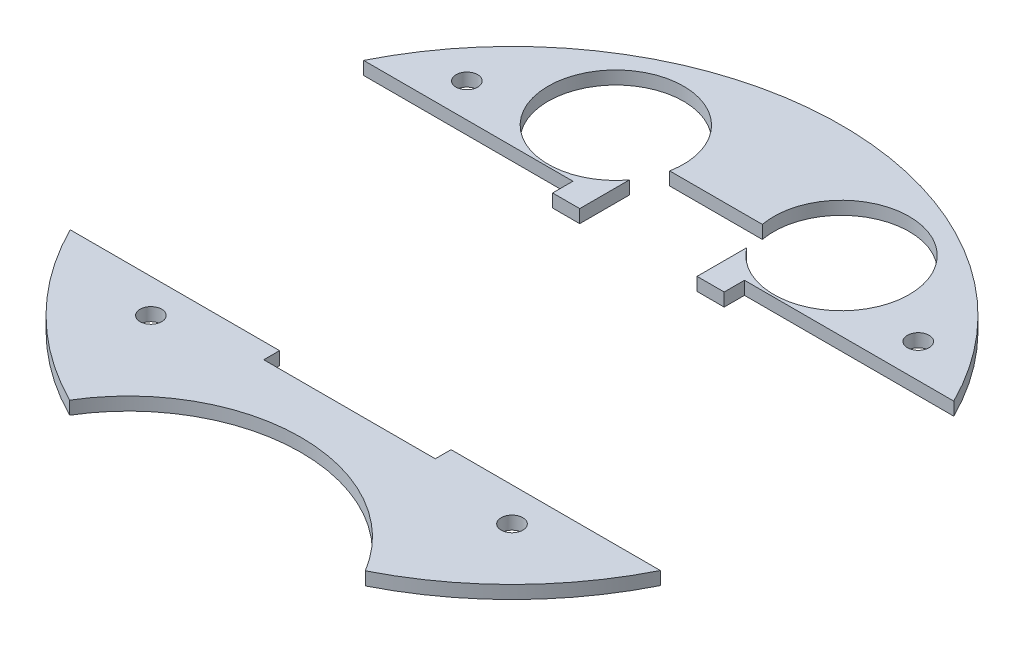
SolidWorks part; units mm, degrees
material "Acrylic (Medium-high impact)"
ref_plane "Front Plane" through (0, 0, 0) normal (0, 0, 1) x (1, 0, 0)
ref_plane "Top Plane" through (0, 0, 0) normal (0, 1, 0) x (1, 0, 0)
ref_plane "Right Plane" through (0, 0, 0) normal (1, 0, 0) x (0, 0, -1)
sketch "Sketch1" plane through (0, 0, 0) normal (0, 1, 0) x (1, 0, 0)
  line L0 (0, -85) -> (-32.7511, -65.2408) construction
  line L1 (0, -85) -> (0, 0) construction
  arc A0 (32.7511, -65.2408) -> (-32.7511, -65.2408) centre (0, 0) ccw
  arc A1 (32.7511, -65.2408) -> (-32.7511, -65.2408) centre (0, -85) ccw
  dimension "D1" = 146
  dimension "D2" = 76.5
  dimension "D3" = 85
extrude "Boss-Extrude1" add sketch "Sketch1" along normal blind 2.9
sketch "solenoid placement" plane through (0, 2.9, 0) normal (0, 1, 0) x (1, 0, 0)
  line L4 (-19, -36) -> (19, -36)
  line L5 (-19, -36) -> (19, -36)
  line L6 (19, -36) -> (19, 28)
  line L7 (19, -36) -> (19, 28)
  line L8 (19, 28) -> (-19, 28)
  line L9 (19, 28) -> (-19, 28)
  line L10 (-19, 28) -> (-19, -36)
  line L11 (-19, 28) -> (-19, -36)
  circle A1 centre (0, 0) radius 73 construction
  arc A2 (32.7511, -65.2408) -> (-32.7511, -65.2408) centre (0, 0) ccw construction
  dimension "D1" = 0
extrude "Cut-Extrude1" cut sketch "solenoid placement" against normal through all
sketch "Sketch3" plane through (0, 2.9, 0) normal (0, 1, 0) x (1, 0, 0)
  circle A1 centre (25, 48) radius 12
  circle A2 centre (-25, 48) radius 12
  dimension "D1" = 24
extrude "Cut-Extrude3" cut sketch "Sketch3" against normal through all
sketch "Sketch4" plane through (0, 5.8, 0) normal (0, 1, 0) x (1, 0, 0)
  circle A1 centre (40, -40) radius 2.4
  circle A2 centre (40, -40) radius 2.4
  circle A3 centre (-40, -40) radius 2.4
  circle A4 centre (-40, -40) radius 2.4
  circle A5 centre (-50, 40) radius 2.4
  circle A6 centre (-50, 40) radius 2.4
  circle A7 centre (50, 40) radius 2.4
  circle A8 centre (50, 40) radius 2.4
  dimension "D1" = 0
  dimension "D2" = 0
  dimension "D3" = 0
  dimension "D4" = 0
extrude "Cut-Extrude4" cut sketch "Sketch4" against normal through all
sketch "Sketch2" plane through (0, 2.9, 0) normal (0, 1, 0) x (1, 0, 0)
  line L0 (-19, 28) -> (-19, 32.5)
  line L1 (-73, -32.5) -> (73, -32.5)
  line L2 (-73, -32.5) -> (-73, 32.5)
  line L3 (-73, 32.5) -> (-19, 32.5)
  line L4 (73, -32.5) -> (73, 32.5)
  line L5 (-73, -32.5) -> (73, 32.5) construction
  line L6 (-73, 32.5) -> (73, -32.5) construction
  line L7 (19, 28) -> (19, 32.5)
  line L8 (19, 28) -> (-19, 28)
  line L9 (19, 32.5) -> (73, 32.5)
  arc A0 (32.7511, -65.2408) -> (-32.7511, -65.2408) centre (0, 0) ccw construction
  point P0 (0, 0)
  dimension "D1" = 65
extrude "Cut-Extrude2" cut sketch "Sketch2" against normal through all
sketch "Sketch5" plane through (0, 2.9, 0) normal (0, 1, 0) x (1, 0, 0)
  line L4 (-13, 28) -> (13, 28)
  line L5 (13, 28) -> (13, 43.2)
  line L6 (11, 45.2) -> (-11, 45.2)
  line L7 (-13, 43.2) -> (-13, 28)
  line L8 (-13, 28) -> (13, 28)
  line L9 (13, 28) -> (13, 43.2)
  line L10 (11, 45.2) -> (-11, 45.2)
  line L11 (-13, 43.2) -> (-13, 28)
  arc A2 (13, 43.2) -> (11, 45.2) centre (11, 43.2) ccw
  arc A3 (-11, 45.2) -> (-13, 43.2) centre (-11, 43.2) ccw
  arc A4 (13, 43.2) -> (11, 45.2) centre (11, 43.2) ccw
  arc A5 (-11, 45.2) -> (-13, 43.2) centre (-11, 43.2) ccw
  dimension "D1" = 0
extrude "Cut-Extrude5" cut sketch "Sketch5" against normal through all
sketch "Sketch6" plane through (0, 2.9, 0) normal (0, 1, 0) x (-1, 0, 0)
  circle A1 centre (-25, -48) radius 15
  circle A2 centre (-25, -48) radius 15
  circle A3 centre (25, -48) radius 15
  circle A4 centre (25, -48) radius 15
  dimension "D1" = 0
  dimension "D2" = 0
extrude "Cut-Extrude10" cut sketch "Sketch6" against normal through all
equation "\"smallPulleyTeeth\"= 15"
equation "\"largePulleyTeeth\"= 30"
equation "\"eighthThick\"= 2.9mm"
equation "\"sixteenthThick\" = 1.7mm"
equation "\"quarterThick\"=6.0mm"
equation "\"OD\" = 146mm"
equation "\"puckAngle\" = 60.5deg"
equation "\"D1@Sketch1\"=\"OD\""
equation "\"puckDiam\" = 76.5mm"
equation "\"D2@Sketch1\"=\"puckDiam\""
equation "\"D1@Boss-Extrude1\"=\"eighthThick\""
equation "\"axlePress\" = 5.9mm"
equation "\"press\" = 0.2mm"
equation "\"wheelClear\" = 0.3mm"
equation "\"10-32clear\" = 4.8mm"
equation "\"6-32clear\" = 3.3mm"
equation "\"8-32clear\" = 4.0mm"
equation "\"wheelHeight\" = 22mm"
equation "\"wheelWell\" = 65mm"
equation "\"D1@Sketch2\"=\"wheelWell\""
equation "\"puckDist\" = 85mm"
equation "\"scoopFillet\" = 5mm"
equation "\"4-40clear\" = 3.0mm"
equation "\"D3@Sketch1\"=\"puckDist\""
